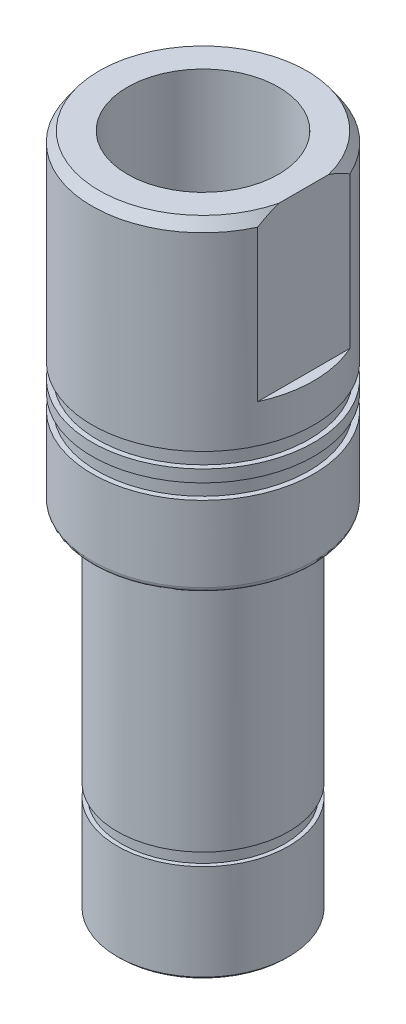
SolidWorks part; units mm, degrees
ref_plane "Front Plane" through (0, 0, 0) normal (0, 0, 1) x (1, 0, 0)
ref_plane "Top Plane" through (0, 0, 0) normal (0, 1, 0) x (1, 0, 0)
ref_plane "Right Plane" through (0, 0, 0) normal (1, 0, 0) x (0, 0, -1)
sketch "Sketch3" plane through (0, 0, 0) normal (0, 1, 0) x (1, 0, 0)
  circle A0 centre (0, 0) radius 8.5
  circle A1 centre (0, 0) radius 7
  dimension "D1" = 17
  dimension "D2" = 14
extrude "Boss-Extrude1" add sketch "Sketch3" along normal blind 35
sketch "Sketch4" plane through (0, 35, 0) normal (0, 1, 0) x (1, 0, 0)
  circle A0 centre (0, 0) radius 11
  circle A2 centre (0, 0) radius 7 construction
  circle A3 centre (0, 0) radius 7
  dimension "D1" = 22
extrude "Boss-Extrude2" add sketch "Sketch4" along normal blind 32
ref_plane "Plane1" through (0, 43, 0) normal (0, 1, 0) x (1, 0, 0)
ref_plane "Plane2" through (0, 45.7, 0) normal (0, 1, 0) x (1, 0, 0)
sketch "Sketch6" plane through (0, 43, 0) normal (0, 1, 0) x (1, 0, 0)
  circle A1 centre (0, 0) radius 11 construction
  circle A2 centre (0, 0) radius 11
sketch "Sketch7" plane through (0, 45.7, 0) normal (0, 1, 0) x (1, 0, 0)
  circle A1 centre (0, 0) radius 11 construction
  circle A2 centre (0, 0) radius 11
sketch "Sketch9" plane through (0, 0, 0) normal (1, 0, 0) x (0, 0, -1)
  line L0 (11, 43) -> (11, 44.5)
  line L2 (11, 44.5) -> (10.5, 44.5)
  line L3 (10.5, 44.5) -> (10.5, 43)
  line L4 (10.5, 43) -> (11, 43)
  line L5 (11, 45.7) -> (11, 47.2)
  line L7 (11, 47.2) -> (10.5, 47.2)
  line L8 (10.5, 47.2) -> (10.5, 45.7)
  line L9 (10.5, 45.7) -> (11, 45.7)
  line L10 (11, 43) -> (-11, 43) construction
  line L11 (11, 45.7) -> (-11, 45.7) construction
  line L12 (11, 43) -> (-11, 43) construction
  line L13 (11, 45.7) -> (-11, 45.7) construction
  dimension "D3" = 1.5
  dimension "D4" = 0.5
sweep "Cut-Sweep1" cut profiles "Sketch9" path "Sketch6"
sketch "Sketch11" plane through (0, 67, 0) normal (0, 1, 0) x (1, 0, 0)
  line L0 (0, 0) -> (10, 0) construction
  line L2 (10, 5) -> (12, 5)
  line L3 (12, 5) -> (12, -5)
  line L4 (12, -5) -> (10, -5)
  line L6 (10, 5) -> (10, -5)
  point P3 (10, 0)
  dimension "D1" = 10
  dimension "D2" = 2
  dimension "D3" = 10
extrude "Cut-Extrude1" cut sketch "Sketch11" against normal blind 16
chamfer "Chamfer2" distance 1 angle 35 1 edges at (-11, 67, 0) first distance on face at (5, 59, 0)
fillet "Fillet1" radius 0.5 1 edges at (0, 35, 11)
chamfer "Chamfer3" distance 0.25 angle 45 1 edges at (0, 0, 8.5)
sketch "Sketch14" plane through (0, 67, 0) normal (0, 1, 0) x (1, 0, 0)
  circle A0 centre (0, 0) radius 7.5
  dimension "D1" = 15
extrude "Cut-Extrude3" cut sketch "Sketch14" against normal blind 12
sketch "Sketch12" plane through (0, 0, 0) normal (0, -1, 0) x (-1, 0, 0)
  circle A0 centre (0, 0) radius 4.5
  circle A3 centre (0, 0) radius 7 construction
  circle A4 centre (0, 0) radius 7
  dimension "D1" = 9
extrude "Boss-Extrude3" add sketch "Sketch12" against normal blind 3 from offset 2 separate body offset against normal yes
extrude "Boss-Extrude4" add sketch "Sketch12<2>" against normal blind 11 from surface separate body starting at face at (0, 5, -4.5)
sketch "Sketch12<2>" plane through (0, 0, 0) normal (0, -1, 0) x (-1, 0, 0) same geometry as "Sketch12"
combine bodies "Combine1" operation type add bodies to combine 108 107
sketch "Sketch13" plane through (0, 0, 0) normal (0, -1, 0) x (1, 0, 0)
  line L0 (1.5, 5.8095) -> (1.5, 4.2426)
  line L1 (5.8095, 1.5) -> (4.2426, 1.5)
  line L10 (-1.5, 5.8095) -> (-1.5, 4.2426)
  line L11 (5.8095, -1.5) -> (4.2426, -1.5)
  line L12 (1.5, -5.8095) -> (1.5, -4.2426)
  line L13 (-1.5, -5.8095) -> (-1.5, -4.2426)
  line L14 (-5.8095, -1.5) -> (-4.2426, -1.5)
  line L15 (-5.8095, 1.5) -> (-4.2426, 1.5)
  circle A1 centre (0, 0) radius 4.5 construction
  circle A2 centre (0, 0) radius 4.5
  circle A3 centre (0, 0) radius 6
  point P23 (0, 0)
  dimension "D1" = 12
  dimension "D2" = 3
  dimension "D3" = 1.5
  dimension "D4" = 4
extrude "Cut-Extrude2" cut sketch "Sketch13" against normal through all contours L15 A3 L14 A2 | L0 A3 L10 A2 | L11 A3 L1 A2 | L13 A3 L12 A2 | A2 region at (0, 0, 5.1752) region at (5.1752, 0, 0) region at (-5.1752, 0, 0) region at (0, 0, -5.1752)
sketch "Sketch15" plane through (0, 0, 0) normal (0, -1, 0) x (1, 0, 0)
  circle A0 centre (0, 0) radius 8.1
  circle A1 centre (0, 0) radius 8.75
  dimension "D1" = 16.2
extrude "Cut-Extrude4" cut sketch "Sketch15" along normal blind 1.25 from offset 11 offset against normal yes
equation "\"D1@Sketch11\"=(22/2)-1"
equation "\"D3@Sketch13\"=\"D2@Sketch13\"/2"
